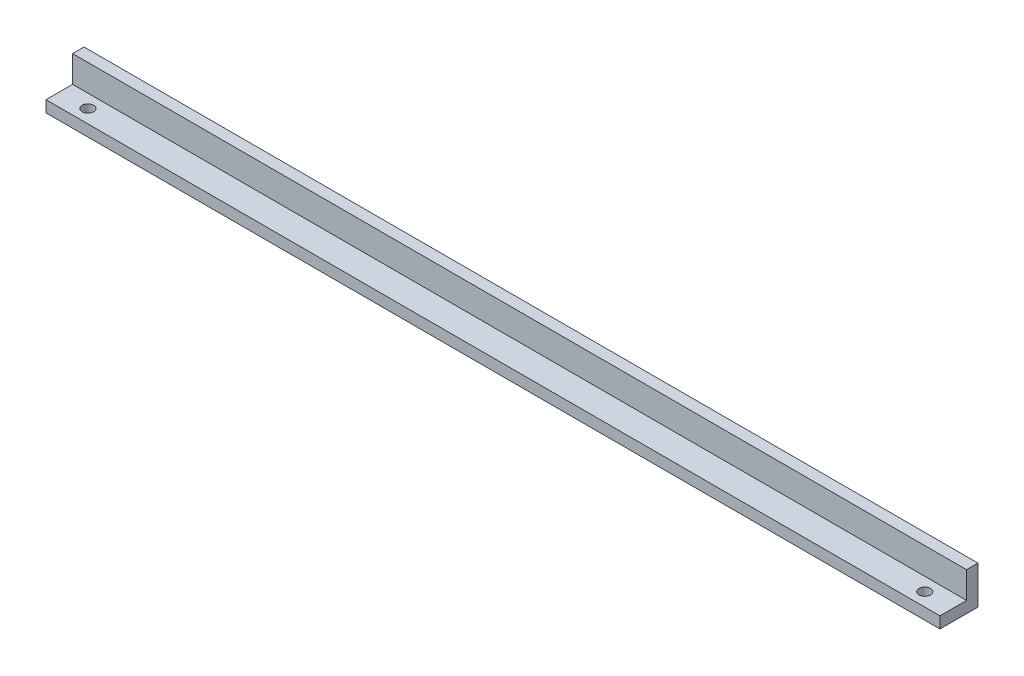
SolidWorks part; units mm, degrees
ref_plane "Спереди" through (0, 0, 0) normal (0, 0, 1) x (1, 0, 0)
ref_plane "Сверху" through (0, 0, 0) normal (0, 1, 0) x (1, 0, 0)
ref_plane "Справа" through (0, 0, 0) normal (1, 0, 0) x (0, 0, -1)
sketch "Эскиз1" plane through (0, 0, 0) normal (1, 0, 0) x (0, 0, -1)
  line L0 (0, 0) -> (-10, 0)
  line L1 (-10, 0) -> (-10, 3)
  line L2 (-10, 3) -> (-3, 3)
  line L3 (-3, 10) -> (-3, 3)
  line L6 (-3, 10) -> (0, 10)
  line L7 (0, 10) -> (0, 0)
  dimension "D1" = 3
  dimension "D2" = 10
extrude "Бобышка-Вытянуть1" add sketch "Эскиз1" along normal blind 235
sketch "Эскиз3" plane through (0, 3, 0) normal (0, 1, 0) x (1, 0, 0)
  line L0 (0, -3) -> (0, -10) construction
  line L1 (235, -10) -> (0, -10) construction
  line L2 (117.5, -10) -> (117.5, 0) construction
  line L3 (235, 0) -> (0, 0) construction
  circle A0 centre (7.5, -6.5) radius 1.5
  circle A1 centre (227.5, -6.5) radius 1.5
  dimension "D1" = 3
  dimension "D2" = 7.5
  dimension "D3" = 3.5
extrude "Вырез-Вытянуть1" cut sketch "Эскиз3" against normal blind 10
